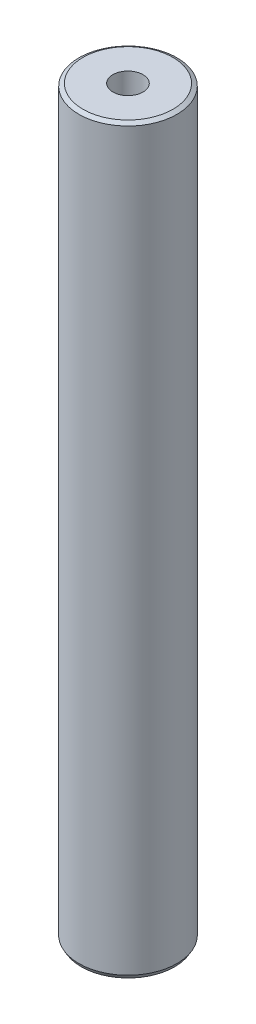
SolidWorks part; units mm, degrees
ref_plane "Front Plane" through (0, 0, 0) normal (0, 0, 1) x (1, 0, 0)
ref_plane "Top Plane" through (0, 0, 0) normal (0, 1, 0) x (1, 0, 0)
ref_plane "Right Plane" through (0, 0, 0) normal (1, 0, 0) x (0, 0, -1)
sketch "Sketch1" plane through (0, 0, 0) normal (0, 1, 0) x (1, 0, 0)
  circle A0 centre (0, 0) radius 35
  dimension "SHAFT_OD" = 70
extrude "Boss-Extrude1" add sketch "Sketch1" along normal blind 529.4795
sketch "Sketch2" plane through (0, 0, 0) normal (0, 1, 0) x (1, 0, 0)
  circle A0 centre (0, 0) radius 10.7696
  dimension "BORE_D" = 21.5391
extrude "Cut-Extrude1" cut sketch "Sketch2" along normal through all
chamfer "Chamfer1" distance 1.6676 angle 60 2 edges at (0, 529.4795, 35) (0, 0, 35) first distance on face at (0, 529.4795, 35) first distance on face at (0, 0, 10.7696)
